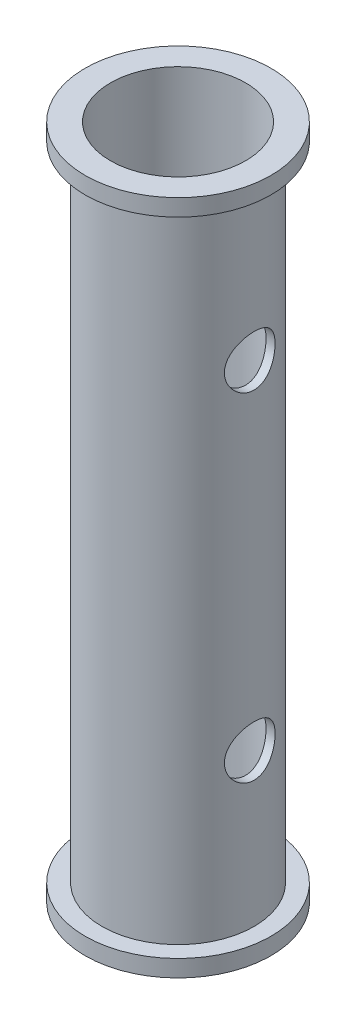
SolidWorks part; units mm, degrees
ref_plane "Front Plane" through (0, 0, 0) normal (0, 0, 1) x (1, 0, 0)
ref_plane "Top Plane" through (0, 0, 0) normal (0, 1, 0) x (1, 0, 0)
ref_plane "Right Plane" through (0, 0, 0) normal (1, 0, 0) x (0, 0, -1)
sketch "Sketch1" plane through (0, 0, 0) normal (0, 1, 0) x (1, 0, 0)
  circle A0 centre (0, 0) radius 4
  circle A1 centre (0, 0) radius 4.5
  circle A2 centre (0, 0) radius 5.5
  dimension "D1" = 8
  dimension "D2" = 9
  dimension "D3" = 11
extrude "Boss-Extrude1" add sketch "Sketch1" along normal blind 1 contours A2 A1 | A1 A0 region at (-4.3727, 0, 0) region at (-5.3444, 0, 0)
extrude "Boss-Extrude2" add sketch "Sketch1<3>" along normal blind 40 contours A1 A0 region at (-4.3727, 0, 0)
sketch "Sketch1<3>" plane through (0, 0, 0) normal (0, 1, 0) x (1, 0, 0) same geometry as "Sketch1"
extrude "Boss-Extrude3" add sketch "Sketch1<4>" along normal blind 1 from offset 39 contours A2 A1 region at (-5.3444, 0, 0)
sketch "Sketch1<4>" plane through (0, 0, 0) normal (0, 1, 0) x (1, 0, 0) same geometry as "Sketch1"
ref_plane "Plane1" through (4.5, 0, 0) normal (1, 0, 0) x (0, 0, -1)
sketch "Sketch2" plane through (4.5, 0, 0) normal (1, 0, 0) x (0, 0, -1)
  line L0 (-5.5, 0) -> (5.5, 0) construction
  line L1 (5.5, 40) -> (-5.5, 40) construction
  circle A0 centre (0, 10) radius 1.5
  circle A1 centre (0, 30) radius 1.5
  dimension "D1" = 3
  dimension "D2" = 3
  dimension "D3" = 10
  dimension "D4" = 10
extrude "Cut-Extrude1" cut sketch "Sketch2" against normal blind 32
